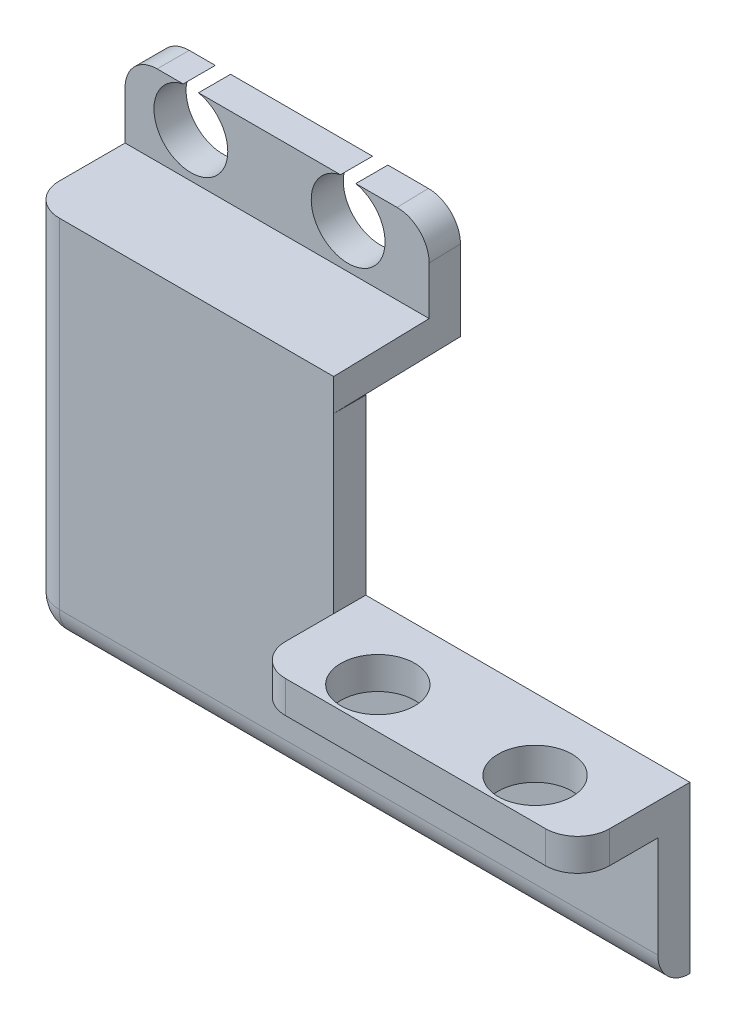
SolidWorks part; units mm, degrees
ref_plane "前视基准面" through (0, 0, 0) normal (0, 0, 1) x (1, 0, 0)
ref_plane "上视基准面" through (0, 0, 0) normal (0, 1, 0) x (1, 0, 0)
ref_plane "右视基准面" through (0, 0, 0) normal (1, 0, 0) x (0, 0, -1)
sketch "草图1" plane through (0, 0, 0) normal (0, 0, 1) x (1, 0, 0)
  line L0 (-10.1, 10.325) -> (10.1, 10.325)
  line L1 (-10.1, 20.65) -> (-10.1, 0) construction
  line L2 (10.1, 20.65) -> (10.1, 0) construction
  line L4 (-10.1, 20.65) -> (10.1, 20.65)
  line L5 (10.1, 20.65) -> (10.1, 10.325)
  line L6 (-10.3, 31.45) -> (-30.1, 31.45) construction
  line L7 (-29.2, 25.9579) -> (-29.2, 5.4243) construction
  line L8 (-29.2, 17.5674) -> (-29.2, 10.325)
  line L9 (-29.2, 10.325) -> (-10.1, 10.325)
  line L10 (-29.2, 17.5674) -> (-29.2, 31.45)
  line L11 (-10.1, 20.65) -> (-10.1, 31.45)
  line L12 (-10.1, 31.45) -> (-29.2, 31.45)
  line L13 (-10.1, 20.65) -> (10.1, 20.65) construction
extrude "凸台-拉伸1" add sketch "草图1" along normal blind 2
sketch "草图2" plane through (0, 0, 2) normal (0, 0, 1) x (1, 0, 0)
  line L0 (-10.1, 20.65) -> (-10.1, 18.65)
  line L1 (-10.1, 18.65) -> (10.1, 18.65)
  line L2 (10.1, 10.325) -> (10.1, 20.65) construction
  line L3 (10.1, 18.65) -> (10.1, 20.65)
  line L4 (10.1, 20.65) -> (-10.1, 20.65)
extrude "凸台-拉伸2" add sketch "草图2" along normal blind 5
fillet "圆角1" radius 2 1 edges at (10.1, 19.65, 7)
fillet "圆角2" radius 2 1 edges at (-10.1, 19.65, 7)
sketch "草图3" plane through (0, 18.65, 0) normal (0, -1, 0) x (1, 0, 0)
  circle A0 centre (-4.9, 4.45) radius 2.3
  arc A1 (-5.377, 6.7) -> (-4.423, 6.7) centre (-4.9, 4.45) ccw construction
  circle A2 centre (4.9, 4.45) radius 2.3
  arc A3 (4.423, 6.7) -> (5.377, 6.7) centre (4.9, 4.45) ccw construction
extrude "切除-拉伸1" cut sketch "草图3" against normal blind 2
ref_plane "基准面1" through (-29.2, 10.325, 2) normal (1, 0, 0) x (0, 0, -1)
sketch "草图5" plane through (0, 31.45, 0) normal (0, 1, 0) x (1, 0, 0)
  line L0 (-19.7, 6.1) -> (-10.3, 6.1)
  line L1 (-10.3, 2.1) -> (-10.3, 11.1) construction
  line L2 (-10.3, 6.1) -> (-10.1, -2)
  line L3 (-10.1, -2) -> (-29.2, -2)
  line L4 (-20.7, 6.1) -> (-29.2, 6.1)
  line L5 (-29.2, 6.1) -> (-29.2, -2)
  line L6 (-19.7, 6.1) -> (-20.7, 6.1)
  line L14 (5.0742, -74.75) -> (5.0742, -73.75)
  line L15 (3.9742, -74.75) -> (5.0742, -74.75)
  line L16 (3.9742, -83.5) -> (3.9742, -74.75)
  line L17 (1.0742, -83.5) -> (3.9742, -83.5)
  line L18 (1.0742, -65) -> (1.0742, -83.5)
  line L19 (3.9742, -65) -> (1.0742, -65)
  line L20 (3.9742, -73.75) -> (3.9742, -65)
  line L21 (5.0742, -73.75) -> (3.9742, -73.75)
  line L24 (3.9742, -83.5) -> (3.9742, -74.75)
  line L25 (1.0742, -83.5) -> (3.9742, -83.5)
  line L26 (1.0742, -65) -> (1.0742, -83.5)
  line L27 (3.9742, -65) -> (1.0742, -65)
  line L28 (3.9742, -73.75) -> (3.9742, -65)
  line M9 (-10.1, 0) -> (-29.2, 0)
  line M10 (-29.2, 0) -> (-29.2, -2)
  line M11 (-29.2, -2) -> (-10.1, -2)
  dimension "D1" = 0
extrude "凸台-拉伸3" add sketch "草图5" along normal blind 2 contours L0 L6 L4 L5 L2 M9 | L2 M9 M10 M11 region at (-19.7123, 31.45, -3.046) region at (-19.6623, 31.45, 1.0004)
sketch "草图6" plane through (0, 33.45, 0) normal (0, 1, 0) x (1, 0, 0)
  line L0 (-10.3, 6.1) -> (-10.2506, 4.1006)
  line L1 (-10.3, 6.1) -> (-10.1, -2) construction
  line L2 (-10.2506, 4.1006) -> (-29.2, 4.1006)
  line L4 (-10.3, 6.1) -> (-29.2, 6.1)
  line L5 (-29.2, 6.1) -> (-29.2, 4.1006)
extrude "凸台-拉伸4" add sketch "草图6" along normal blind 5
fillet "圆角3" radius 2 1 edges at (-10.2753, 38.45, -5.1003)
fillet "圆角4" radius 2 1 edges at (-29.2, 38.45, -5.1003)
fillet "圆角5" radius 2 1 edges at (-29.2, 21.8875, 2)
fillet "圆角6" radius 2 2 edges at (-28.6142, 10.325, 1.4142) (-8.55, 10.325, 2)
sketch "草图7" plane through (0, 0, -4.1006) normal (0, 0, 1) x (1, 0, 0)
  circle A1 centre (-15.3, 36.2) radius 2.3
  arc A2 (-15.777, 38.45) -> (-14.823, 38.45) centre (-15.3, 36.2) ccw construction
  circle A3 centre (-25.1, 36.2) radius 2.3
  arc A4 (-25.577, 38.45) -> (-24.623, 38.45) centre (-25.1, 36.2) ccw construction
extrude "切除-拉伸2" cut sketch "草图7" against normal blind 2
